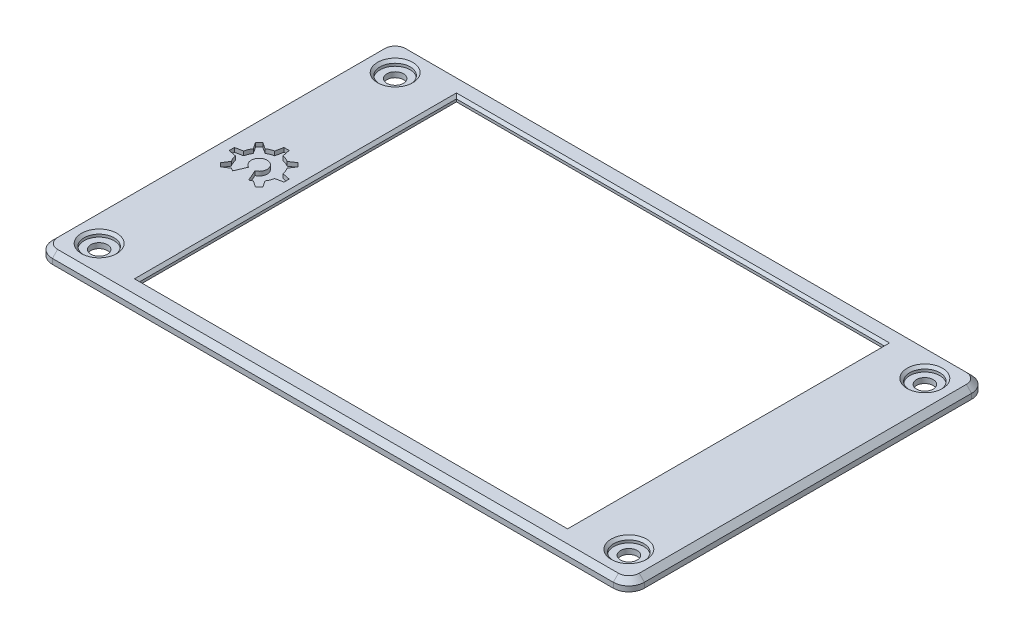
SolidWorks part; units mm, degrees
ref_plane "Front Plane" through (0, 0, 0) normal (0, 0, 1) x (1, 0, 0)
ref_plane "Top Plane" through (0, 0, 0) normal (0, 1, 0) x (1, 0, 0)
ref_plane "Right Plane" through (0, 0, 0) normal (1, 0, 0) x (0, 0, -1)
sketch "Sketch1" plane through (0, 0, 0) normal (0, 1, 0) x (1, 0, 0)
  line L1 (3, 0) -> (111, 0)
  line L2 (0, 3) -> (0, 66)
  line L3 (3, 69) -> (111, 69)
  line L4 (114, 3) -> (114, 66)
  line L5 (15.8, 65) -> (98.2, 65)
  line L6 (15.8, 65) -> (15.8, 4)
  line L7 (15.8, 4) -> (98.2, 4)
  line L8 (98.2, 65) -> (98.2, 4)
  arc A0 (0, 3) -> (3, 0) centre (3, 3) ccw
  arc A1 (111, 0) -> (114, 3) centre (111, 3) ccw
  arc A2 (114, 66) -> (111, 69) centre (111, 66) ccw
  arc A3 (3, 69) -> (0, 66) centre (3, 66) ccw
  circle A4 centre (6, 63) radius 1.6
  circle A5 centre (6, 6) radius 1.6
  circle A6 centre (108, 6) radius 1.6
  circle A7 centre (108, 63) radius 1.6
  point P7 (0, 0)
  point P10 (114, 0)
  point P15 (0, 69)
  dimension "D3" = 3
  dimension "D4" = 3.2
  dimension "D1" = 69
  dimension "D2" = 114
  dimension "D5" = 6
  dimension "D6" = 6
  dimension "D7" = 6
  dimension "D8" = 6
  dimension "D9" = 82.4
  dimension "D10" = 61
  dimension "D11" = 15.8
  dimension "D12" = 4
extrude "Boss-Extrude1" add sketch "Sketch1" along normal blind 2
sketch "Sketch2" plane through (0, 0, 0) normal (0, -1, 0) x (1, 0, 0)
  line L8 (14.8, -66) -> (99.2, -66)
  line L9 (99.2, -66) -> (99.2, -3)
  line L10 (99.2, -3) -> (14.8, -3)
  line L11 (14.8, -3) -> (14.8, -66)
  line L12 (14.8, -66) -> (99.2, -66)
  line L13 (99.2, -66) -> (99.2, -3)
  line L14 (99.2, -3) -> (14.8, -3)
  line L15 (14.8, -3) -> (14.8, -66)
  dimension "D1" = 1
extrude "Cut-Extrude1" cut sketch "Sketch2" against normal blind 1
chamfer "Chamfer1" distance 0.5 angle 45 4 edges at (98.2, 2, -34.5) (57, 2, -65) (15.8, 2, -34.5) (57, 2, -4)
sketch "Sketch3" plane through (0, 2, 0) normal (0, 1, 0) x (1, 0, 0)
  circle A0 centre (6, 63) radius 2.9
  circle A1 centre (108, 63) radius 2.9
  circle A2 centre (108, 6) radius 2.9
  circle A3 centre (6, 6) radius 2.9
  dimension "D1" = 5.8
extrude "Cut-Extrude2" cut sketch "Sketch3" against normal blind 1
chamfer "Chamfer2" distance 0.5 angle 45 4 edges at (108, 2, -3.1) (108, 2, -60.1) (6, 2, -3.1) (6, 2, -60.1)
chamfer "Chamfer3" distance 1 angle 45 8 edges at (113.1213, 2, -0.8787) (114, 2, -34.5) (113.1213, 2, -68.1213) (57, 2, -69) (0.8787, 2, -68.1213) (0, 2, -34.5) (0.8787, 2, -0.8787) (57, 2, 0)
sketch "Sketch4" plane through (0, 2, 0) normal (0, 1, 0) x (1, 0, 0)
  line L1 (9.8254, 30.9603) -> (8.8959, 33.1186)
  line L2 (8.2907, 34.5239) -> (12.0383, 38.2715) construction
  line L35 (8.2907, 34.5239) -> (12.0383, 30.7762) construction
  line L36 (8.2907, 39.8002) -> (8.7907, 39.8002)
  line L37 (11.6681, 38.6084) -> (12.0216, 38.2548)
  line L38 (12.0216, 38.2548) -> (12.3752, 37.9013)
  line L39 (13.567, 35.0239) -> (13.567, 34.5239)
  line L40 (13.567, 34.5239) -> (13.567, 34.0239)
  line L41 (12.3752, 31.1465) -> (12.0216, 30.7929)
  line L42 (12.0216, 30.7929) -> (11.6681, 30.4394)
  line L43 (8.7907, 39.8002) -> (9.0907, 38.3205)
  line L44 (10.4096, 37.7742) -> (11.6681, 38.6084)
  line L45 (12.3752, 37.9013) -> (11.541, 36.6428)
  line L46 (13.567, 35.0239) -> (12.0873, 35.3239)
  line L47 (13.567, 34.0239) -> (12.0873, 33.7239)
  line L48 (12.3752, 31.1465) -> (11.541, 32.4049)
  line L49 (11.6681, 30.4394) -> (10.4096, 31.2736)
  line L50 (8.2907, 39.8002) -> (7.7907, 39.8002)
  line L51 (7.7907, 39.8002) -> (7.4907, 38.3205)
  line L52 (6.1717, 37.7742) -> (4.9133, 38.6084)
  line L53 (4.9133, 38.6084) -> (4.5597, 38.2548)
  line L54 (4.5597, 38.2548) -> (4.2062, 37.9013)
  line L55 (4.2062, 37.9013) -> (5.0404, 36.6428)
  line L56 (4.494, 35.3239) -> (3.0143, 35.0239)
  line L57 (3.0143, 35.0239) -> (3.0143, 34.5239)
  line L58 (3.0143, 34.5239) -> (3.0143, 34.0239)
  line L59 (3.0143, 34.0239) -> (4.494, 33.7239)
  line L60 (5.0404, 32.4049) -> (4.2062, 31.1465)
  line L61 (4.2062, 31.1465) -> (4.5597, 30.7929)
  line L62 (4.5597, 30.7929) -> (4.9133, 30.4394)
  line L63 (4.9133, 30.4394) -> (6.1717, 31.2736)
  line L64 (6.756, 30.9603) -> (7.6855, 33.1186)
  circle A0 centre (8.2907, 34.5239) radius 1.53 construction
  circle A1 centre (8.2907, 34.5239) radius 3.88 construction
  circle A2 centre (8.2907, 34.5239) radius 5.3 construction
  arc A3 (6.1717, 31.2736) -> (6.756, 30.9603) centre (8.2907, 34.5239) ccw
  arc A4 (9.8254, 30.9603) -> (10.4096, 31.2736) centre (8.2907, 34.5239) ccw
  arc A5 (11.541, 32.4049) -> (12.0873, 33.7239) centre (8.2907, 34.5239) ccw
  arc A6 (12.0873, 35.3239) -> (11.541, 36.6428) centre (8.2907, 34.5239) ccw
  arc A7 (10.4096, 37.7742) -> (9.0907, 38.3205) centre (8.2907, 34.5239) ccw
  arc A8 (7.4907, 38.3205) -> (6.1717, 37.7742) centre (8.2907, 34.5239) ccw
  arc A9 (5.0404, 36.6428) -> (4.494, 35.3239) centre (8.2907, 34.5239) ccw
  arc A10 (4.494, 33.7239) -> (5.0404, 32.4049) centre (8.2907, 34.5239) ccw
  arc A11 (8.8959, 33.1186) -> (7.6855, 33.1186) centre (8.2907, 34.5239) ccw
  point P0 (0, 0)
  point P59 (0, 0)
extrude "Cut-Extrude3" cut sketch "Sketch4" against normal blind 0.8
